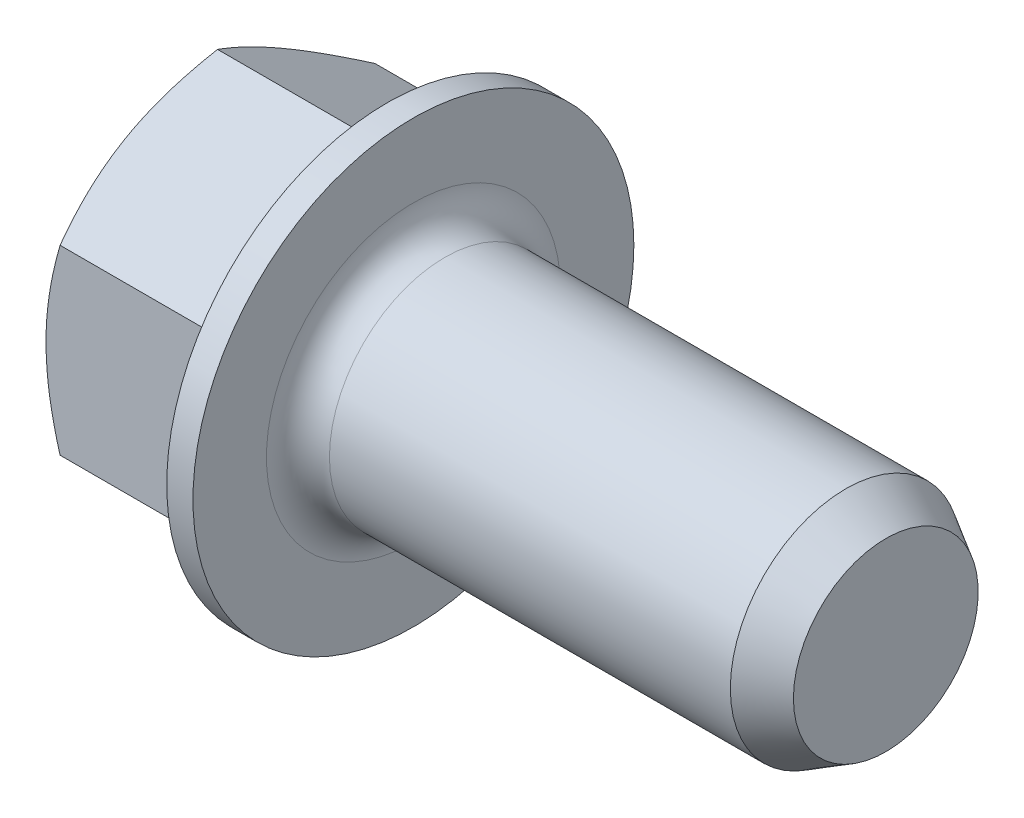
SolidWorks part; units mm, degrees
ref_plane "Front" through (0, 0, 0) normal (0, 0, 1) x (1, 0, 0)
ref_plane "Top" through (0, 0, 0) normal (0, 1, 0) x (1, 0, 0)
ref_plane "Right" through (0, 0, 0) normal (1, 0, 0) x (0, 0, -1)
sketch "Sketch1" plane through (0, 0, 0) normal (0, 0, 1) x (1, 0, 0)
  line L0 (0, 0) -> (0, 1.32)
  line L1 (0, 1.32) -> (1.75, 1.32)
  line L2 (2, 2.1) -> (2, 1.1)
  line L3 (1.75, 1.32) -> (1.75, 2.1)
  line L4 (2, 1.1) -> (6.5, 1.1)
  line L5 (6.5, 1.1) -> (6.5, 0)
  line L6 (6.5, 0) -> (0, 0)
  line L7 (13.1079, 0) -> (-2.2203, 0) construction
  line L8 (1.75, 2.1) -> (2, 2.1)
  dimension "k" = 2
revolve "Revolve1" add sketch "Sketch1" angle 360 about L7
cosmetic thread "ThreadCosmetic" [suppressed] parameters "D2"=1.63
sketch "Sketch2" plane through (0, 0, 0) normal (-1, 0, 0) x (0, 0, 1)
  line L1 (1.5, -0.866) -> (1.5, 0.866)
  line L2 (1.5, 0.866) -> (0, 1.7321)
  line L3 (0, 1.7321) -> (-1.5, 0.866)
  line L4 (-1.5, 0.866) -> (-1.5, -0.866)
  line L5 (-1.5, -0.866) -> (0, -1.7321)
  line L6 (0, -1.7321) -> (1.5, -0.866)
  circle A0 centre (0, 0) radius 1.5 construction
extrude "Extrude1" add sketch "Sketch2" against normal blind 2
sketch "Sketch3" plane through (0, 0, 0) normal (0, 1, 0) x (1, 0, 0)
  line L0 (-0.866, 0) -> (7.7942, 15)
  line L2 (0, 0) -> (-2.2444, 0) construction
  line L5 (7.7942, 15) -> (-0.966, 15)
  line L6 (-0.866, 0) -> (-0.966, 0)
  line L7 (-0.966, 0) -> (-0.966, 15)
  dimension "D1" = 60
  dimension "D2" = 30
  dimension "D3" = 0.1
revolve "Cut-Revolve2" cut sketch "Sketch3" angle 360 about L2
sketch "Sketch4" plane through (0, 0, 0) normal (0, 0, 1) x (1, 0, 0)
  line L0 (0, 0) -> (1.9538, 0) construction
  line L1 (-0.2, 0) -> (-0.2, 1.2)
  line L2 (-0.2, 1.2) -> (0.85, 1.2)
  line L3 (0.85, 1.2) -> (0.85, 0)
  line L5 (1.75, 2.1) -> (1.75, -2.1) construction
  line L6 (0.85, 0) -> (-0.2, 0)
  line L7 (1.75, 2.1) -> (1.75, -2.1) construction
  dimension "D1" = 0.2
  dimension "D2" = 2.4
  dimension "k'" = 0.9
revolve "Cut-Revolve3" cut sketch "Sketch4" angle 360 about L0
chamfer "Chamfer1" distance 0.22 angle 60 1 edges at (6.5, 0, -1.1) first distance on face at (6.5, 0, -1.1)
sketch "Sketch6" plane through (0, 0, 0) normal (0, 0, 1) x (1, 0, 0)
  line L0 (2.7155, 0.815) -> (2.2445, 0.815)
  line L1 (2.2445, 0.815) -> (2.08, 1.1)
  line L2 (2.7155, 0.815) -> (2.88, 1.1)
  line L3 (2.08, 1.1) -> (2.08, 1.35)
  line L4 (2.88, 1.1) -> (2.88, 1.35)
  line L5 (2.08, 1.35) -> (2.88, 1.35)
  line L6 (2.48, 0.815) -> (2.48, 0) construction
  line L7 (0, 0) -> (7.3035, 0) construction
  dimension "D2" = 60
  dimension "D3" = 0.25
  dimension "minordia" = 1.63
  dimension "threadstart" = 2.48
  dimension "D1" = 2.2
revolve "ThreadSchematic" [suppressed] cut sketch "Sketch6" angle 360 about L7
pattern_linear "ThdSchPat" [suppressed] count 6 spacing 0.8 along (1, 0, 0) of bodies 139
sketch "Sketch5" plane through (0, 0, 0) normal (0, 0, 1) x (1, 0, 0)
  line L1 (6.5, 1.1) -> (6.5, 0) construction
  line L3 (3.5, -1.1) -> (4.7, -1.1) construction
  line L4 (0, 0) -> (6.648, 0) construction
  line L5 (6.5, 0) -> (4.7, -1.1)
  line L6 (6.5, 0) -> (6.7, 0)
  line L7 (6.7, 0) -> (6.7, -1.3)
  line L8 (6.7, -1.3) -> (4.7, -1.3)
  line L9 (4.7, -1.3) -> (4.7, -1.1)
  line L10 (4.7, -1.1) -> (6.8602, -1.1) construction
  dimension "D1" = 0.2
  dimension "D3" = 0.2
  dimension "D4" = 2.2
  dimension "y" = 2
revolve "EndCone" [suppressed] cut sketch "Sketch5" angle 360 about L4
fillet "Fillet1" radius 0.3 1 edges at (2, 0, -1.1)
fillet "Fillet2" radius 0.2 6 edges at (1.75, -1.299, -0.75) (1.75, 0, -1.5) (1.75, 1.299, -0.75) (1.75, -1.299, 0.75) (1.75, 0, 1.5) (1.75, 1.299, 0.75)
equation "\"minordia@Sketch6\" = \"D2@ThreadCosmetic\""
equation "\"D1@Extrude1\" = \"k@Sketch1\""
equation "\"D2@Sketch4\" = \"s@Sketch2\" * 4 / 5"
equation "\"D1@Chamfer1\" = \"d@Sketch1\" / 10"
equation "\"threadstart@Sketch6\" = \"D1@Extrude1\"+(\"advance@Sketch6\"*0.6)"
equation "\"D1@ThdSchPat\" = int((\"l@Sketch1\"/\"advance@Sketch6\") + 0.8)"
equation "\"D3@ThdSchPat\" = \"advance@Sketch6\""
equation "\"D1@Sketch6\" = \"d@Sketch1\""
equation "\"D4@Sketch5\" = \"d@Sketch1\""
equation "\"da@Sketch1\" = \"d@Sketch1\"*1.2"
